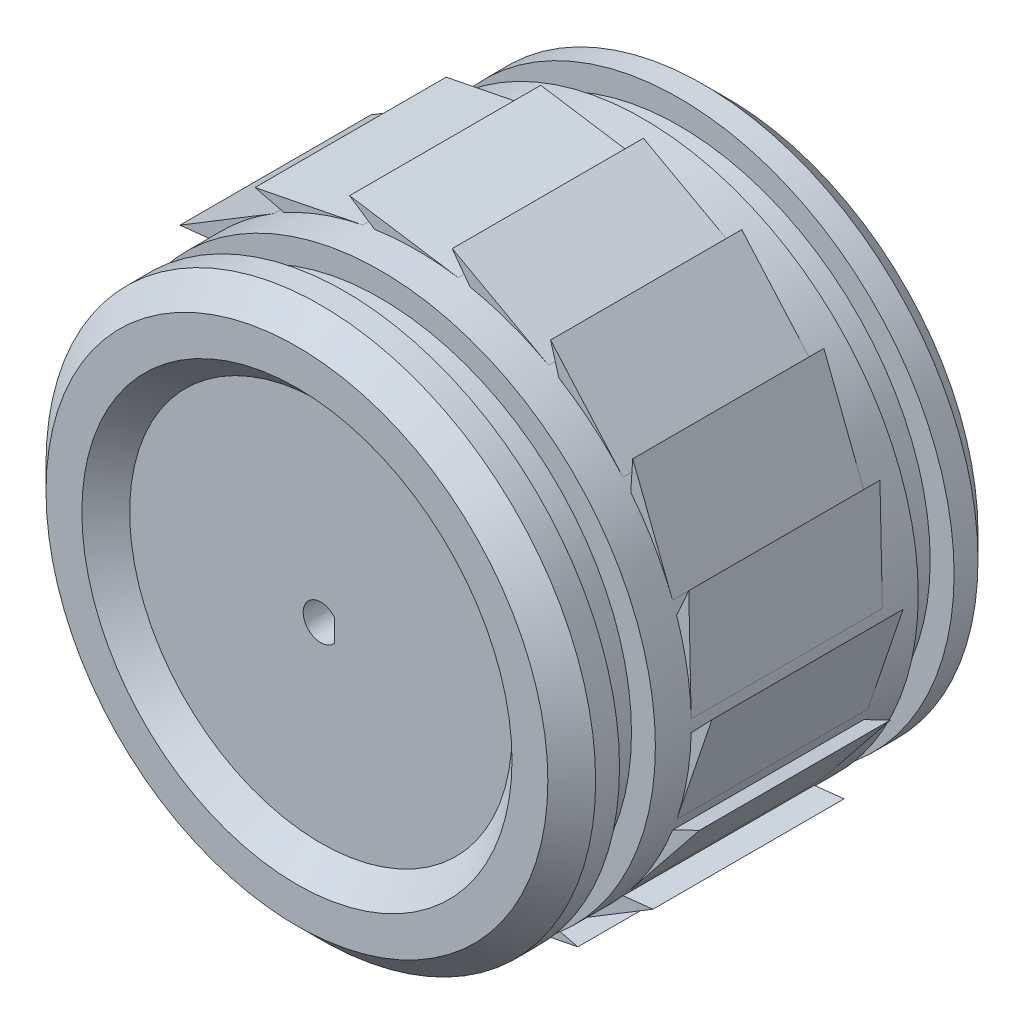
SolidWorks part; units mm, degrees
material "ABS"
ref_plane "Спереди" through (0, 0, 0) normal (0, 0, 1) x (1, 0, 0)
ref_plane "Сверху" through (0, 0, 0) normal (0, 1, 0) x (1, 0, 0)
ref_plane "Справа" through (0, 0, 0) normal (1, 0, 0) x (0, 0, -1)
sketch "Эскиз1" plane through (0, 0, 0) normal (1, 0, 0) x (0, 0, -1)
  line L0 (0, 22.5472) -> (0, -23.5635) construction
  line L1 (0, 23) -> (-16, 23)
  line L2 (-18, 21) -> (-18, 18)
  line L5 (-16, 16) -> (-16, 0)
  line L9 (16, 23) -> (0, 23)
  line L10 (-28.6739, 0) -> (34.4859, 0) construction
  line L11 (-18, 18) -> (-16, 16)
  line L12 (18, 21) -> (16, 23)
  line L14 (-16, 0) -> (-14.3343, 0)
  line L15 (-12, 10) -> (-12, 13.5)
  line L16 (-8, 17.5) -> (18, 17.5)
  line L17 (18, 17.5) -> (18, 21)
  line L19 (-16, 23) -> (-18, 21)
  line L20 (-12, 13.5) -> (-8, 17.5)
  line L21 (-16, 16) -> (-18, 16) construction
  line L22 (-14.3343, 0) -> (-6, 0)
  line L25 (-6, 0) -> (-6, 3.0803)
  line L26 (-18, 16) -> (-18, 23) construction
  line L27 (-18, 23) -> (-16, 23) construction
  line L28 (16, 23) -> (18, 23) construction
  line L29 (18, 23) -> (18, 21) construction
  spline S0 degree 3 poles (-12, 10) (-11.4798, 10) (-6.662, 9.4441) (-6, 4.0945) (-6, 3.0803) knots 0 0 0 0 0.356151 1 1 1 1
  point P4 (-18, 23)
  point P6 (-18, 16)
  point P10 (-12, 17.5)
  point P11 (18, 23)
  dimension "D1" = 35
  dimension "D2" = 4
  dimension "D4" = 20
  dimension "D5" = 6
  dimension "D9" = 3
  dimension "D8" = 36
  dimension "D11" = 46
ref_axis "Ось1" through (0, 0, -80.9) along (0, 0, 1)
revolve "Повернуть1" add sketch "Эскиз1" angle 360 about L10 region at (0, 22.5728, -8)
sketch "Эскиз2" plane through (0, 0, 16) normal (0, 0, 1) x (1, 0, 0)
  line L0 (1.125, 0.9539) -> (1.125, -0.9539)
  circle A0 centre (0, 0) radius 1.475
  point P5 (-1.475, 0)
  dimension "D1" = 2.95
  dimension "D2" = 2.6
extrude "Вырез-Вытянуть1" cut sketch "Эскиз2" against normal through all contours L0 A0 region at (-0.0907, 0, 16)
ref_plane "Плоскость1" through (0, 20, 0) normal (0, 1, 0) x (1, 0, 0)
sketch "Эскиз3" plane through (0, 0, 0) normal (1, 0, 0) x (0, 0, -1)
  line L0 (-27.6376, 0) -> (18.0085, 0) construction
  line L1 (18, 21) -> (16, 23)
  line L2 (16, 23) -> (14, 23)
  line L3 (16, 23) -> (-16, 23) construction
  line L4 (14, 23) -> (14, 21)
  line L5 (14, 21) -> (11, 21)
  line L6 (11, 21) -> (11, 23)
  line L7 (11, 23) -> (-11, 23)
  line L8 (-11, 23) -> (-11, 21)
  line L9 (-11, 21) -> (-14, 21)
  line L10 (-14, 21) -> (-14, 23)
  line L11 (-14, 23) -> (-16, 23)
  line L12 (-16, 23) -> (-18, 21)
  line L13 (-18, 21) -> (-18, 24.3347)
  line L14 (-18, 24.3347) -> (18, 24.3347)
  line L15 (18, 24.3347) -> (18, 21)
  dimension "D1" = 2
  dimension "D2" = 2
  dimension "D3" = 3
  dimension "D4" = 3
  dimension "D5" = 2
revolve "Вырез-Повернуть1" cut sketch "Эскиз3" angle 360 about L0
sketch "Эскиз4" plane through (0, 0, 0) normal (0, 0, 1) x (1, 0, 0)
  line L0 (0, 25.4704) -> (0, -25.2707) construction
  line L1 (-3.5, 22.7321) -> (-5.5929, 24.1321)
  line L2 (-5.5929, 24.1321) -> (3.5, 22.7321)
  line L3 (2.9981, 24.5897) -> (11.0638, 20.1641)
  line L4 (4.4859, 22.5583) -> (2.9981, 24.5897)
  line L5 (11.2275, 22.0813) -> (17.2931, 15.1641)
  line L6 (11.9308, 19.6636) -> (11.2275, 22.0813)
  line L7 (18.1026, 16.9096) -> (21.4366, 8.335)
  line L8 (17.9366, 14.3972) -> (18.1026, 16.9096)
  line L9 (22.7943, 9.6984) -> (22.9946, 0.5006)
  line L10 (21.779, 7.3942) -> (22.7943, 9.6984)
  line L11 (24.7367, 1.3174) -> (21.779, -7.3942)
  line L12 (22.9946, -0.5006) -> (24.7367, 1.3174)
  line L13 (23.6955, -7.2225) -> (17.9366, -14.3972)
  line L14 (21.4366, -8.335) -> (23.6955, -7.2225)
  line L15 (19.7962, -14.8913) -> (11.9308, -19.6636)
  line L16 (17.2931, -15.1641) -> (19.7962, -14.8913)
  line L17 (13.5092, -20.7639) -> (4.4859, -22.5583)
  line L18 (11.0638, -20.1641) -> (13.5092, -20.7639)
  line L19 (5.5929, -24.1321) -> (-3.5, -22.7321)
  line L20 (3.5, -22.7321) -> (5.5929, -24.1321)
  line L21 (-2.9981, -24.5897) -> (-11.0638, -20.1641)
  line L22 (-4.4859, -22.5583) -> (-2.9981, -24.5897)
  line L23 (-11.2275, -22.0813) -> (-17.2931, -15.1641)
  line L24 (-11.9308, -19.6636) -> (-11.2275, -22.0813)
  line L25 (-18.1026, -16.9096) -> (-21.4366, -8.335)
  line L26 (-17.9366, -14.3972) -> (-18.1026, -16.9096)
  line L27 (-22.7943, -9.6984) -> (-22.9946, -0.5006)
  line L28 (-21.779, -7.3942) -> (-22.7943, -9.6984)
  line L29 (-24.7367, -1.3174) -> (-21.779, 7.3942)
  line L30 (-22.9946, 0.5006) -> (-24.7367, -1.3174)
  line L31 (-23.6955, 7.2225) -> (-17.9366, 14.3972)
  line L32 (-21.4366, 8.335) -> (-23.6955, 7.2225)
  line L33 (-19.7962, 14.8913) -> (-11.9308, 19.6636)
  line L34 (-17.2931, 15.1641) -> (-19.7962, 14.8913)
  line L35 (-13.5092, 20.7639) -> (-4.4859, 22.5583)
  line L36 (-11.0638, 20.1641) -> (-13.5092, 20.7639)
  arc A0 (3.5, 22.7321) -> (-3.5, 22.7321) centre (0, 0) ccw
  arc A1 (11.0638, 20.1641) -> (4.4859, 22.5583) centre (0, 0) ccw
  circle A2 centre (0, 0) radius 23 construction
  arc A3 (17.2931, 15.1641) -> (11.9308, 19.6636) centre (0, 0) ccw
  arc A4 (21.4366, 8.335) -> (17.9366, 14.3972) centre (0, 0) ccw
  arc A5 (22.9946, 0.5006) -> (21.779, 7.3942) centre (0, 0) ccw
  arc A6 (21.779, -7.3942) -> (22.9946, -0.5006) centre (0, 0) ccw
  arc A7 (17.9366, -14.3972) -> (21.4366, -8.335) centre (0, 0) ccw
  arc A8 (11.9308, -19.6636) -> (17.2931, -15.1641) centre (0, 0) ccw
  arc A9 (4.4859, -22.5583) -> (11.0638, -20.1641) centre (0, 0) ccw
  arc A10 (-3.5, -22.7321) -> (3.5, -22.7321) centre (0, 0) ccw
  arc A11 (-11.0638, -20.1641) -> (-4.4859, -22.5583) centre (0, 0) ccw
  arc A12 (-17.2931, -15.1641) -> (-11.9308, -19.6636) centre (0, 0) ccw
  arc A13 (-21.4366, -8.335) -> (-17.9366, -14.3972) centre (0, 0) ccw
  arc A14 (-22.9946, -0.5006) -> (-21.779, -7.3942) centre (0, 0) ccw
  arc A15 (-21.779, 7.3942) -> (-22.9946, 0.5006) centre (0, 0) ccw
  arc A16 (-17.9366, 14.3972) -> (-21.4366, 8.335) centre (0, 0) ccw
  arc A17 (-11.9308, 19.6636) -> (-17.2931, 15.1641) centre (0, 0) ccw
  arc A18 (-4.4859, 22.5583) -> (-11.0638, 20.1641) centre (0, 0) ccw
  point P63 (0, 0)
  dimension "D1" = 7
  dimension "D2" = 1.4
  dimension "D3" = 18
extrude "Бобышка-Вытянуть1" add sketch "Эскиз4" along normal mid plane 16
equation "\"D2@Эскиз3\"=\"D1@Эскиз3\""
equation "\"D4@Эскиз3\"=\"D3@Эскиз3\""
